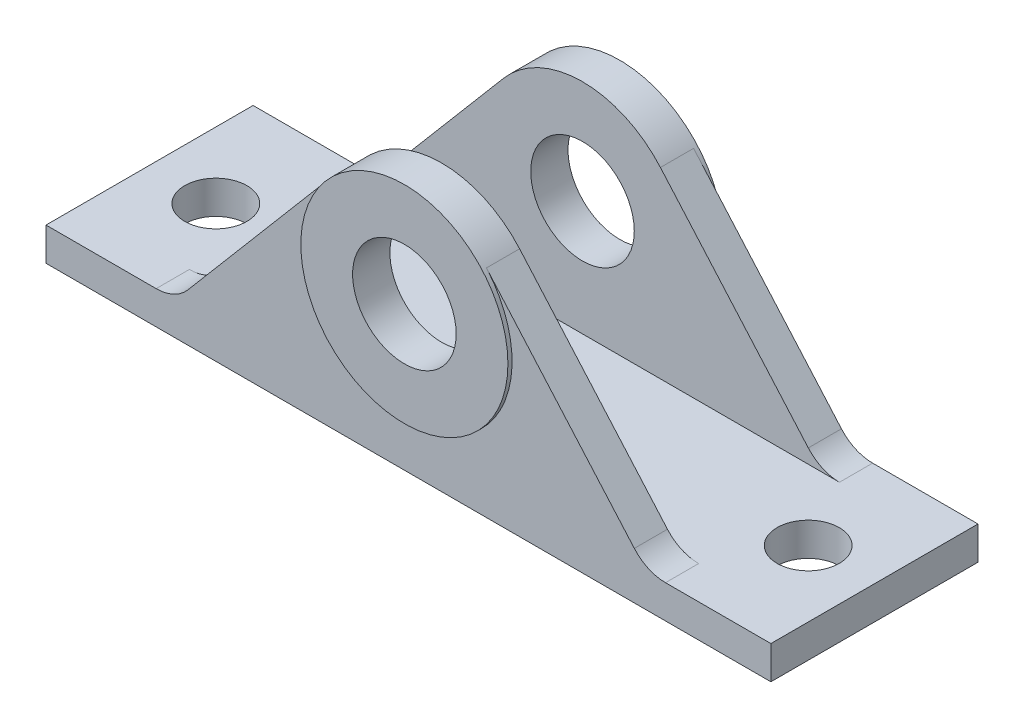
SolidWorks part; units mm, degrees
ref_plane "Front Plane" through (0, 0, 0) normal (0, 0, 1) x (1, 0, 0)
ref_plane "Top Plane" through (0, 0, 0) normal (0, 1, 0) x (1, 0, 0)
ref_plane "Right Plane" through (0, 0, 0) normal (1, 0, 0) x (0, 0, -1)
sketch "Sketch1" plane through (0, 0, 0) normal (0, 0, 1) x (1, 0, 0)
  line L0 (87.52, 7.7365) -> (87.52, 49.1887) construction
  line L1 (0, 0) -> (175, 0)
  line L2 (0, 0) -> (0, 8)
  line L3 (0, 8) -> (26.591, 8)
  line L4 (175, 0) -> (175, 8)
  line L5 (34.2181, 11.5326) -> (68.4523, 51.9051)
  line L6 (106.3326, 52.2013) -> (142.0296, 11.4141)
  line L7 (149.5546, 8) -> (175, 8)
  line L8 (26.591, 8) -> (149.5546, 8)
  line L9 (87.5, -10) -> (87.5, 72.5837) construction
  circle A0 centre (87.52, 35.7365) radius 12.5
  circle A1 centre (87.52, 35.7365) radius 25
  arc A2 (34.2181, 11.5326) -> (26.591, 8) centre (26.591, 18) cw
  arc A3 (149.5546, 8) -> (142.0296, 11.4141) centre (149.5546, 18) cw
  dimension "D2" = 50
  dimension "D3" = 25
  dimension "D5" = 10
  dimension "D6" = 10
  dimension "D1" = 28
  dimension "D4" = 175
  dimension "D7" = 8
extrude "Boss-Extrude1" add sketch "Sketch1" along normal blind 50 contours L8 L3 L2 L1 L4 L7 region at (87.5, 4, 0)
extrude "Boss-Extrude3" add sketch "Sketch1<4>" along normal blind 8 contours L8 A3 L6 A1 L5 A2 region at (30.8487, 8.8074, 0)
sketch "Sketch1<4>" plane through (0, 0, 0) normal (0, 0, 1) x (1, 0, 0) same geometry as "Sketch1"
extrude "Boss-Extrude4" add sketch "Sketch1<5>" against normal blind 8 from vertex contours L8 A3 L6 A1 L5 A2 region at (30.8487, 8.8074, 0) starting at point (0, 8, 50)
sketch "Sketch1<5>" plane through (0, 0, 0) normal (0, 0, 1) x (1, 0, 0) same geometry as "Sketch1"
extrude "Boss-Extrude5" add sketch "Sketch1<6>" against normal blind 9 from vertex contours A1 A0 region at (87.3301, 60.0286, 0) starting at point (68.4523, 51.9051, 8)
sketch "Sketch1<6>" plane through (0, 0, 0) normal (0, 0, 1) x (1, 0, 0) same geometry as "Sketch1"
extrude "Boss-Extrude7" add sketch "Sketch1<8>" along normal blind 9 from vertex contours A1 starting at point (106.3326, 52.2013, 42)
sketch "Sketch1<8>" plane through (0, 0, 0) normal (0, 0, 1) x (1, 0, 0) same geometry as "Sketch1"
extrude "Cut-Extrude1" cut sketch "Sketch1<10>" along normal through all both and the other way through all contours A0 region at (87.52, 35.7365, 0)
sketch "Sketch1<10>" plane through (0, 0, 0) normal (0, 0, 1) x (1, 0, 0) same geometry as "Sketch1"
sketch "Sketch2" plane through (0, 8, 0) normal (0, 1, 0) x (1, 0, 0)
  line L0 (0, -25) -> (175, -25) construction
  line L1 (0, -50) -> (0, 0) construction
  line L2 (175, -50) -> (175, 0) construction
  line L3 (0, -25) -> (16, -25) construction
  line L4 (175, -25) -> (159, -25) construction
  circle A0 centre (16, -25) radius 7.5
  circle A1 centre (159, -25) radius 7.5
  dimension "D3" = 15
  dimension "D4" = 15
  dimension "D1" = 16
  dimension "D2" = 16
extrude "Cut-Extrude2" cut sketch "Sketch2" against normal through all both and the other way through all contours A0 | A1 region at (16, 8, 25) region at (159, 8, 25)
